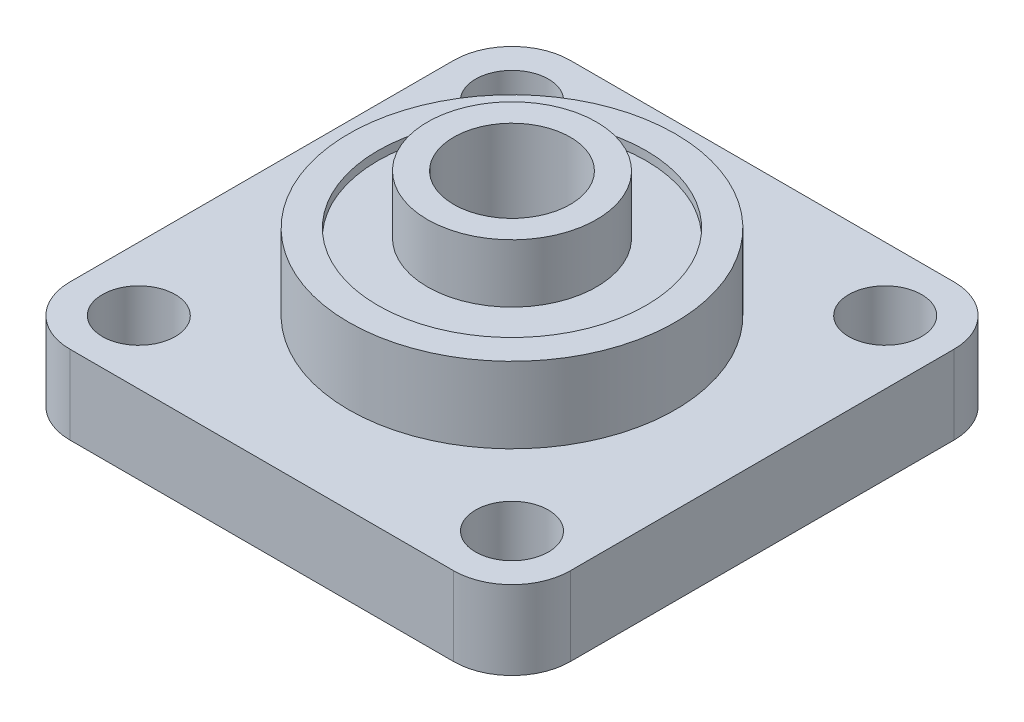
SolidWorks part; units mm, degrees
ref_plane "前视基准面" through (0, 0, 0) normal (0, 0, 1) x (1, 0, 0)
ref_plane "上视基准面" through (0, 0, 0) normal (0, 1, 0) x (1, 0, 0)
ref_plane "右视基准面" through (0, 0, 0) normal (1, 0, 0) x (0, 0, -1)
sketch "草图1" plane through (0, 0, 0) normal (0, 0, 1) x (1, 0, 0)
  line L0 (0, 50.9425) -> (0, 0) construction
  line L1 (0, 0) -> (58.6416, 0) construction
  line L2 (10, 30) -> (14.5, 30)
  line L3 (14.5, 30) -> (14.5, 20)
  line L4 (14.5, 20) -> (23, 20)
  line L5 (23, 20) -> (23, 21.5)
  line L6 (23, 21.5) -> (28, 21.5)
  line L7 (28, 21.5) -> (28, 3.5)
  line L8 (28, 3.5) -> (14.5, 3.5)
  line L9 (14.5, 3.5) -> (14.5, 0)
  line L10 (14.5, 0) -> (10, 0)
  line L11 (10, 0) -> (10, 30)
  point P6 (28, 12.5)
  dimension "D1" = 14.5
  dimension "D2" = 10
  dimension "D3" = 8.5
  dimension "D4" = 28
  dimension "D5" = 10
  dimension "D6" = 30
  dimension "D7" = 3.5
  dimension "D8" = 5
revolve "旋转1" add sketch "草图1" angle 360 about L0
ref_plane "基准面1" through (0, -5, 0) normal (0, 1, 0) x (1, 0, 0)
sketch "草图2" plane through (0, -5, 0) normal (0, 1, 0) x (1, 0, 0)
  line L1 (-42.9, 42.9) -> (42.9, 42.9)
  line L2 (-42.9, 42.9) -> (-42.9, -42.9)
  line L3 (-42.9, -42.9) -> (42.9, -42.9)
  line L4 (42.9, 42.9) -> (42.9, -42.9)
  line L5 (-42.9, 42.9) -> (42.9, -42.9) construction
  line L6 (-42.9, -42.9) -> (42.9, 42.9) construction
  circle A0 centre (-32, 32) radius 6.25
  circle A1 centre (32, 32) radius 6.25
  circle A2 centre (32, -32) radius 6.25
  circle A3 centre (-32, -32) radius 6.25
  point P0 (0, 0)
  point P8 (0, 0)
  point P9 (28.7831, 28.7831)
  point P10 (0, 0)
  dimension "D2" = 12.5
  dimension "D4" = 64
  dimension "D1" = 85.8
  dimension "D3" = 4
extrude "凸台-拉伸1" add sketch "草图2" along normal blind 13.5
fillet "圆角1" radius 10 4 edges at (42.9, 1.75, 42.9) (42.9, 1.75, -42.9) (-42.9, 1.75, -42.9) (-42.9, 1.75, 42.9)
sketch "草图3" plane through (0, 8.5, 0) normal (0, 1, 0) x (1, 0, 0)
  circle A1 centre (0, 0) radius 10
  circle A2 centre (0, 0) radius 10
  dimension "D1" = 0
extrude "切除-拉伸1" cut sketch "草图3" against normal through all
